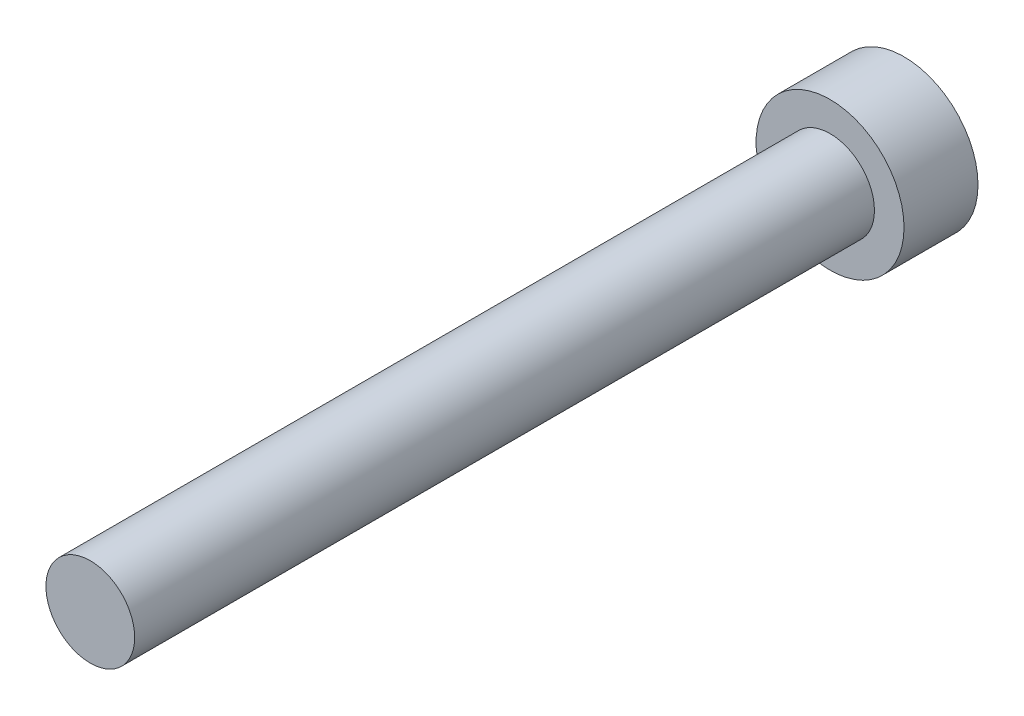
SolidWorks part; units mm, degrees
material "Chrome Stainless Steel"
ref_plane "Front Plane" through (0, 0, 0) normal (0, 0, 1) x (1, 0, 0)
ref_plane "Top Plane" through (0, 0, 0) normal (0, 1, 0) x (1, 0, 0)
ref_plane "Right Plane" through (0, 0, 0) normal (1, 0, 0) x (0, 0, -1)
sketch "Sketch1" plane through (0, 0, 0) normal (0, 0, 1) x (1, 0, 0)
  circle A0 centre (0, 0) radius 2.5
  circle A1 centre (0, 0) radius 1.5
  dimension "D1" = 5
  dimension "D2" = 3
extrude "Boss-Extrude3" add sketch "Sketch1" against normal blind 2.5 contours A0 A1 | A1 region at (-2.4293, 0, 0) region at (0, 0, 0)
extrude "Boss-Extrude4" add sketch "Sketch1<3>" along normal blind 25 contours A1 region at (0, 0, 0)
sketch "Sketch1<3>" plane through (0, 0, 0) normal (0, 0, 1) x (1, 0, 0) same geometry as "Sketch1"
